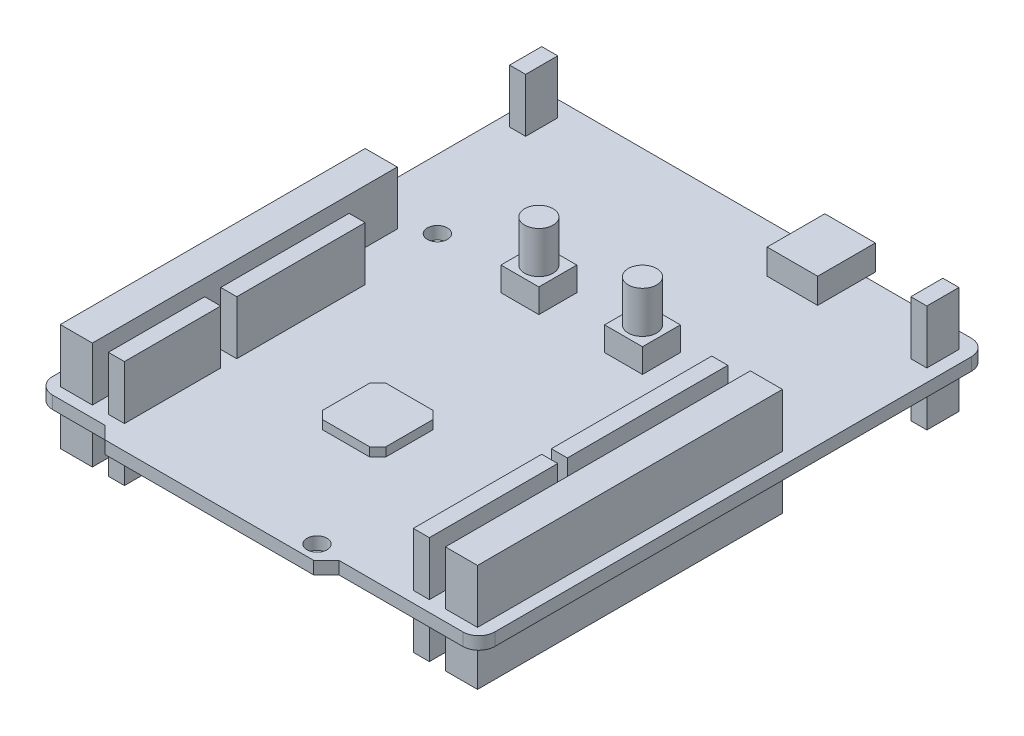
SolidWorks part; units mm, degrees
ref_plane "Front Plane" through (0, 0, 0) normal (0, 0, 1) x (1, 0, 0)
ref_plane "Top Plane" through (0, 0, 0) normal (0, 1, 0) x (1, 0, 0)
ref_plane "Right Plane" through (0, 0, 0) normal (1, 0, 0) x (0, 0, -1)
sketch "Sketch1" plane through (0, 0, 0) normal (0, 1, 0) x (1, 0, 0)
  line L1 (-35, 41.25) -> (35, 41.25)
  line L2 (-35, 41.25) -> (-35, -41.25)
  line L3 (-35, -41.25) -> (35, -41.25)
  line L4 (35, 41.25) -> (35, -41.25)
  line L5 (-35, 41.25) -> (35, -41.25) construction
  line L6 (-35, -41.25) -> (35, 41.25) construction
  point P0 (0, 0)
  dimension "D1" = 82.5
  dimension "D2" = 70
extrude "Boss-Extrude1" add sketch "Sketch1" along normal blind 2
sketch "Sketch2" plane through (0, 2, 0) normal (0, 1, 0) x (1, 0, 0)
  line L0 (-35, -41.25) -> (-35, -39.25)
  line L1 (-35, 41.25) -> (-35, -41.25) construction
  line L2 (-35, -39.25) -> (-24.13, -39.25)
  line L3 (-24.13, -39.25) -> (-22.13, -41.25)
  line L4 (-35, -41.25) -> (35, -41.25) construction
  line L5 (-22.13, -41.25) -> (-35, -41.25)
  line L6 (35, -39.25) -> (12.87, -39.25)
  line L7 (35, -41.25) -> (35, 41.25) construction
  line L8 (12.87, -39.25) -> (10.87, -41.25)
  line L9 (10.87, -41.25) -> (35, -41.25)
  line L10 (35, -41.25) -> (35, -39.25)
  line L11 (-22.13, -41.25) -> (10.87, -41.25) construction
  line L12 (27.94, 10.78) -> (33.02, 10.78)
  line L13 (-33.02, 10.78) -> (-27.94, 10.78)
  line L14 (-33.02, 10.78) -> (-33.02, -37.48)
  line L15 (-33.02, -37.48) -> (-27.94, -37.48)
  line L16 (-27.94, 10.78) -> (-27.94, -37.48)
  line L17 (27.94, 10.78) -> (27.94, -37.48)
  line L18 (27.94, -37.48) -> (33.02, -37.48)
  line L19 (33.02, 10.78) -> (33.02, -37.48)
  line L20 (-30.48, -34.94) -> (-33.02, -37.48) construction
  line L21 (-33.02, -37.48) -> (-30.48, -37.48) construction
  line L22 (-33.02, -37.48) -> (-33.02, -34.94) construction
  line L23 (-33.02, -34.94) -> (-30.48, -34.94) construction
  line L24 (-30.48, -37.48) -> (-30.48, -34.94) construction
  line L25 (-27.94, -34.94) -> (-30.48, -34.94) construction
  line L26 (-27.94, -34.94) -> (-27.94, -37.48) construction
  line L27 (-27.94, -37.48) -> (-30.48, -37.48) construction
  line L28 (-30.48, -34.94) -> (-30.48, -37.48) construction
  line L29 (30.48, -34.94) -> (33.02, -37.48) construction
  line L30 (33.02, -37.48) -> (30.48, -37.48) construction
  line L31 (33.02, -37.48) -> (33.02, -34.94) construction
  line L32 (33.02, -34.94) -> (30.48, -34.94) construction
  line L33 (30.48, -37.48) -> (30.48, -34.94) construction
  line L34 (0, 41.25) -> (0, -41.25) construction
  line L35 (35, 41.25) -> (-35, 41.25) construction
  line L36 (-27.94, -13.35) -> (27.94, -13.35) construction
  line L37 (-22.86, -37.48) -> (22.86, -37.48) construction
  line L38 (22.86, 9.76) -> (25.4, 9.76)
  line L39 (22.86, 9.76) -> (22.86, -15.64)
  line L40 (22.86, -15.64) -> (25.4, -15.64)
  line L41 (25.4, 9.76) -> (25.4, -15.64)
  line L42 (22.86, -17.16) -> (25.4, -17.16)
  line L43 (22.86, -17.16) -> (22.86, -37.48)
  line L44 (22.86, -37.48) -> (25.4, -37.48)
  line L45 (25.4, -17.16) -> (25.4, -37.48)
  line L46 (-22.86, 0.62) -> (-25.4, 0.62)
  line L47 (-22.86, 0.62) -> (-22.86, -19.7)
  line L48 (-22.86, -19.7) -> (-25.4, -19.7)
  line L49 (-25.4, 0.62) -> (-25.4, -19.7)
  line L50 (-25.4, -22.24) -> (-22.86, -22.24)
  line L51 (-25.4, -22.24) -> (-25.4, -37.48)
  line L52 (-25.4, -37.48) -> (-22.86, -37.48)
  line L53 (-22.86, -22.24) -> (-22.86, -37.48)
  line L54 (-24.13, 0.62) -> (-24.13, 41.25) construction
  line L55 (24.13, 9.76) -> (24.13, 41.25) construction
  line L56 (-33.02, 36.18) -> (-30.48, 33.64) construction
  line L57 (-33.02, 38.72) -> (-30.48, 38.72)
  line L58 (-33.02, 38.72) -> (-33.02, 33.64)
  line L59 (-33.02, 33.64) -> (-30.48, 33.64)
  line L60 (-30.48, 38.72) -> (-30.48, 33.64)
  line L61 (-33.02, 36.18) -> (-30.48, 38.72) construction
  line L63 (33.02, 38.72) -> (30.48, 38.72)
  line L64 (33.02, 38.72) -> (33.02, 33.64)
  line L65 (33.02, 33.64) -> (30.48, 33.64)
  line L66 (30.48, 38.72) -> (30.48, 33.64)
  circle A0 centre (8.89, -38.75) radius 1.5875
  circle A1 centre (24.13, 12.05) radius 1.5875
  circle A2 centre (-24.13, 13.32) radius 1.5875
  point P30 (-30.48, -37.48)
  point P34 (-31.75, -36.21)
  point P35 (31.75, -36.21)
  point P43 (0, -13.35)
  point P60 (0, -37.48)
  point P71 (-24.13, -37.48)
  point P75 (-31.75, 34.91)
  point P76 (-31.75, 37.45)
  dimension "D6" = 3.175
  dimension "D23" = 2.29
  dimension "D1" = 33
  dimension "D2" = 10.87
  dimension "D3" = 45
  dimension "D4" = 45
  dimension "D5" = 5.08
  dimension "D7" = 5.08
  dimension "D8" = 48.26
  dimension "D9" = 3.04
  dimension "D10" = 2.54
  dimension "D11" = 2.54
  dimension "D12" = 2.54
  dimension "D13" = 63.5
  dimension "D14" = 2.54
  dimension "D15" = 2.54
  dimension "D16" = 15.24
  dimension "D17" = 20.32
  dimension "D18" = 25.4
  dimension "D19" = 20.32
  dimension "D20" = 2.54
  dimension "D21" = 1.52
  dimension "D22" = 45.72
  dimension "D24" = 12.7
  dimension "D25" = 33.02
  dimension "D26" = 3.8
  dimension "D27" = 71.12
extrude "Cut-Extrude1" cut sketch "Sketch2" against normal through all contours A2 | L2 L3 L5 L0 | L9 L10 L6 L8 | A1 | A0
fillet "Fillet1" radius 2.54 4 edges at (-35, 1, -41.25) (35, 1, -41.25) (35, 1, 39.25) (-35, 1, 39.25)
extrude "Boss-Extrude2" add sketch "Sketch2<3>" along normal mid plane 17 contours L16 L13 L14 L15 | L46 L49 L48 L47 | L53 L50 L51 L52 | L19 L12 L17 L18 | L63 L66 L65 L64 | L60 L59 L58 L57 | L41 L40 L39 L38 | L43 L44 L45 L42 region at (30.48, 2, 13.35) region at (-30.48, 2, 13.35) region at (-24.13, 2, 9.54) region at (-24.13, 2, 29.86) region at (31.75, 2, -36.18)
sketch "Sketch2<3>" plane through (0, 2, 0) normal (0, 1, 0) x (1, 0, 0) same geometry as "Sketch2"
sketch "Sketch4" plane through (0, 2, 0) normal (0, 1, 0) x (1, 0, 0)
  line L1 (7.8, 42.71) -> (15.8, 42.71)
  line L2 (7.8, 42.71) -> (7.8, 33.58)
  line L3 (7.8, 33.58) -> (15.8, 33.58)
  line L4 (15.8, 42.71) -> (15.8, 33.58)
  line L5 (-22.13, -41.25) -> (10.87, -41.25) construction
  line L6 (-11, 16.25) -> (-5, 16.25)
  line L7 (-11, 16.25) -> (-11, 10.25)
  line L8 (-11, 10.25) -> (-5, 10.25)
  line L9 (-5, 16.25) -> (-5, 10.25)
  line L10 (5.4, 16.25) -> (11.4, 16.25)
  line L11 (5.4, 16.25) -> (5.4, 10.25)
  line L12 (5.4, 10.25) -> (11.4, 10.25)
  line L13 (11.4, 16.25) -> (11.4, 10.25)
  line L14 (35, -36.71) -> (35, 38.71) construction
  line L15 (32.46, 41.25) -> (-32.46, 41.25) construction
  dimension "D1" = 6
  dimension "D2" = 8
  dimension "D3" = 57.5
  dimension "D4" = 10.4
  dimension "D5" = 23.6
  dimension "D6" = 19.2
  dimension "D7" = 9.13
  dimension "D8" = 1.46
extrude "Boss-Extrude3" add sketch "Sketch4" along normal blind 4 contours L1 L4 L3 L2
extrude "Boss-Extrude4" add sketch "Sketch4<3>" along normal blind 3.8 contours L9 L6 L7 L8 | L13 L10 L11 L12 region at (-8, 2, -13.25) region at (8.4, 2, -13.25)
sketch "Sketch4<3>" plane through (0, 2, 0) normal (0, 1, 0) x (1, 0, 0) same geometry as "Sketch4"
sketch "Sketch5" plane through (0, 5.8, 0) normal (0, 1, 0) x (1, 0, 0)
  line L0 (-11, 16.25) -> (-5, 10.25) construction
  line L1 (5.4, 16.25) -> (11.4, 10.25) construction
  circle A0 centre (-8, 13.25) radius 2.25
  circle A1 centre (8.4, 13.25) radius 2.25
  dimension "D1" = 4.5
extrude "Boss-Extrude5" add sketch "Sketch5" along normal blind 6.6
sketch "Sketch6" plane through (0, 2, 0) normal (0, 1, 0) x (1, 0, 0)
  line L0 (-35, 38.71) -> (-35, -36.71) construction
  line L1 (-7.6, -12.65) -> (2.4, -12.65)
  line L2 (-7.6, -12.65) -> (-7.6, -22.65)
  line L3 (-7.6, -22.65) -> (2.4, -22.65)
  line L4 (2.4, -12.65) -> (2.4, -22.65)
  line L5 (-7.6, -12.65) -> (2.4, -22.65) construction
  line L6 (-7.6, -22.65) -> (2.4, -12.65) construction
  line L7 (-22.13, -41.25) -> (10.87, -41.25) construction
  point P0 (-2.6, -17.65)
  dimension "D1" = 10
  dimension "D2" = 37.4
  dimension "D3" = 28.6
extrude "Boss-Extrude6" add sketch "Sketch6" along normal blind 1.4
chamfer "Chamfer1" distance 1.27 angle 45 4 edges at (2.4, 2.7, 22.65) (2.4, 2.7, 12.65) (-7.6, 2.7, 12.65) (-7.6, 2.7, 22.65)
